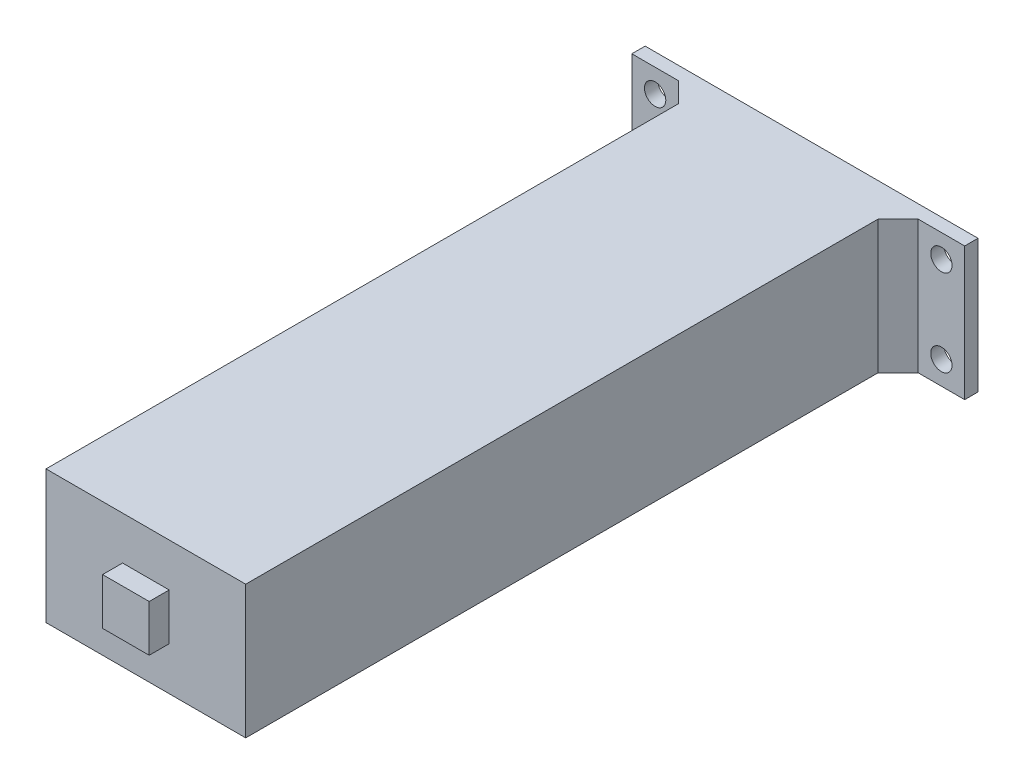
SolidWorks part; units mm, degrees
ref_plane "正面" through (0, 0, 0) normal (0, 0, 1) x (1, 0, 0)
ref_plane "平面" through (0, 0, 0) normal (0, 1, 0) x (1, 0, 0)
ref_plane "右側面" through (0, 0, 0) normal (1, 0, 0) x (0, 0, -1)
sketch "ｽｹｯﾁ1" plane through (0, 0, 0) normal (0, 0, 1) x (1, 0, 0)
  line L1 (-12.7289, 5.1915) -> (17.2711, 5.1915)
  line L2 (-12.7289, 5.1915) -> (-12.7289, -14.8085)
  line L3 (-12.7289, -14.8085) -> (17.2711, -14.8085)
  line L4 (17.2711, 5.1915) -> (17.2711, -14.8085)
  dimension "D1" = 30
  dimension "D2" = 20
extrude "ﾎﾞｽ - 押し出し1" add sketch "ｽｹｯﾁ1" along normal blind 100
sketch "ｽｹｯﾁ3" plane through (17.2711, 0, 0) normal (1, 0, 0) x (0, 0, -1)
  line L0 (-100, -14.8085) -> (0, -14.8085) construction
  line L1 (0, 5.1915) -> (-2, 5.1915)
  line L2 (0, 5.1915) -> (0, -14.8085)
  line L3 (0, -14.8085) -> (-2, -14.8085)
  line L4 (-2, 5.1915) -> (-2, -14.8085)
  dimension "D2" = 2
extrude "ﾎﾞｽ - 押し出し2" add sketch "ｽｹｯﾁ3" along normal blind 10
sketch "ｽｹｯﾁ5" plane through (0, 5.1915, 0) normal (0, 1, 0) x (1, 0, 0)
  line L0 (17.2711, -5) -> (20.2711, -2)
  line L1 (17.2711, -100) -> (17.2711, -2) construction
  line L2 (27.2711, -2) -> (17.2711, -2) construction
  line L3 (20.2711, -2) -> (17.2711, -2)
  line L4 (17.2711, -2) -> (17.2711, -5)
  dimension "D1" = 3
extrude "ﾎﾞｽ - 押し出し3" add sketch "ｽｹｯﾁ5" against normal through all
sketch "ｽｹｯﾁ6" plane through (0, 0, 2) normal (0, 0, 1) x (1, 0, 0)
  line L0 (23.7711, 1.6915) -> (20.2711, 1.6915) construction
  line L1 (20.2711, -14.8085) -> (20.2711, 5.1915) construction
  line L2 (23.7711, 1.6915) -> (27.2711, 1.6915) construction
  line L3 (27.2711, 5.1915) -> (27.2711, -14.8085) construction
  line L4 (23.7711, -11.3085) -> (20.2711, -11.3085) construction
  line L5 (23.7711, -11.3085) -> (27.2711, -11.3085) construction
  line L6 (23.7711, -11.3085) -> (23.7711, -14.8085) construction
  line L7 (27.2711, -14.8085) -> (20.2711, -14.8085) construction
  line L8 (23.7711, 1.6915) -> (23.7711, 5.1915) construction
  line L9 (27.2711, 5.1915) -> (20.2711, 5.1915) construction
  circle A0 centre (23.7711, 1.6915) radius 1.6
  circle A1 centre (23.7711, -11.3085) radius 1.6
  dimension "D1" = 3.2
  dimension "D2" = 3.2
extrude "ｶｯﾄ - 押し出し2" cut sketch "ｽｹｯﾁ6" against normal through all
sketch "ｽｹｯﾁ7" plane through (-12.7289, 0, 0) normal (-1, 0, 0) x (0, 0, 1)
  line L0 (100, 5.1915) -> (0, 5.1915) construction
  line L1 (0, -14.8085) -> (2, -14.8085)
  line L2 (0, -14.8085) -> (0, 5.1915)
  line L3 (0, 5.1915) -> (2, 5.1915)
  line L4 (2, -14.8085) -> (2, 5.1915)
  dimension "D1" = 2
extrude "ﾎﾞｽ - 押し出し4" add sketch "ｽｹｯﾁ7" along normal blind 10
sketch "ｽｹｯﾁ8" plane through (0, -14.8085, 0) normal (0, -1, 0) x (1, 0, 0)
  line L0 (-12.7289, 5) -> (-15.7289, 2)
  line L1 (-12.7289, 100) -> (-12.7289, 2) construction
  line L2 (-22.7289, 2) -> (-12.7289, 2) construction
  line L3 (-15.7289, 2) -> (-12.7289, 2)
  line L4 (-12.7289, 2) -> (-12.7289, 5)
  dimension "D1" = 3
extrude "ﾎﾞｽ - 押し出し5" add sketch "ｽｹｯﾁ8" against normal through all
sketch "ｽｹｯﾁ9" plane through (0, 0, 2) normal (0, 0, 1) x (1, 0, 0)
  line L0 (-19.2289, 1.6915) -> (-15.7289, 1.6915) construction
  line L1 (-15.7289, 5.1915) -> (-15.7289, -14.8085) construction
  line L2 (-19.2289, 1.6915) -> (-22.7289, 1.6915) construction
  line L3 (-22.7289, -14.8085) -> (-22.7289, 5.1915) construction
  line L4 (-19.2289, -11.3085) -> (-22.7289, -11.3085) construction
  line L5 (-19.2289, -11.3085) -> (-15.7289, -11.3085) construction
  line L6 (-19.2289, 1.6915) -> (-19.2289, 5.1915) construction
  line L7 (-22.7289, 5.1915) -> (-15.7289, 5.1915) construction
  line L8 (-19.2289, -11.3085) -> (-19.2289, -14.8085) construction
  line L9 (-22.7289, -14.8085) -> (-15.7289, -14.8085) construction
  circle A0 centre (-19.2289, -11.3085) radius 1.6
  circle A1 centre (-19.2289, 1.6915) radius 1.6
  dimension "D1" = 3.2
  dimension "D2" = 3.2
extrude "ｶｯﾄ - 押し出し3" cut sketch "ｽｹｯﾁ9" against normal through all
sketch "ｽｹｯﾁ10" plane through (0, 0, 100) normal (0, 0, 1) x (1, 0, 0)
  line L0 (2.2711, -4.8085) -> (17.2711, -4.8085) construction
  line L1 (17.2711, -14.8085) -> (17.2711, 5.1915) construction
  line L2 (2.2711, -4.8085) -> (-12.7289, -4.8085) construction
  line L3 (-12.7289, 5.1915) -> (-12.7289, -14.8085) construction
  line L4 (2.2711, -4.8085) -> (2.2711, 5.1915) construction
  line L5 (17.2711, 5.1915) -> (-12.7289, 5.1915) construction
  line L6 (2.2711, -4.8085) -> (2.2711, -14.8085) construction
  line L7 (-12.7289, -14.8085) -> (17.2711, -14.8085) construction
  line L9 (-1.2289, -1.3085) -> (5.7711, -1.3085)
  line L10 (-1.2289, -1.3085) -> (-1.2289, -8.3085)
  line L11 (-1.2289, -8.3085) -> (5.7711, -8.3085)
  line L12 (5.7711, -1.3085) -> (5.7711, -8.3085)
  line L13 (-1.2289, -1.3085) -> (5.7711, -8.3085) construction
  line L14 (-1.2289, -8.3085) -> (5.7711, -1.3085) construction
  dimension "D1" = 7
  dimension "D2" = 7
extrude "ﾎﾞｽ - 押し出し7" add sketch "ｽｹｯﾁ10" along normal blind 3
